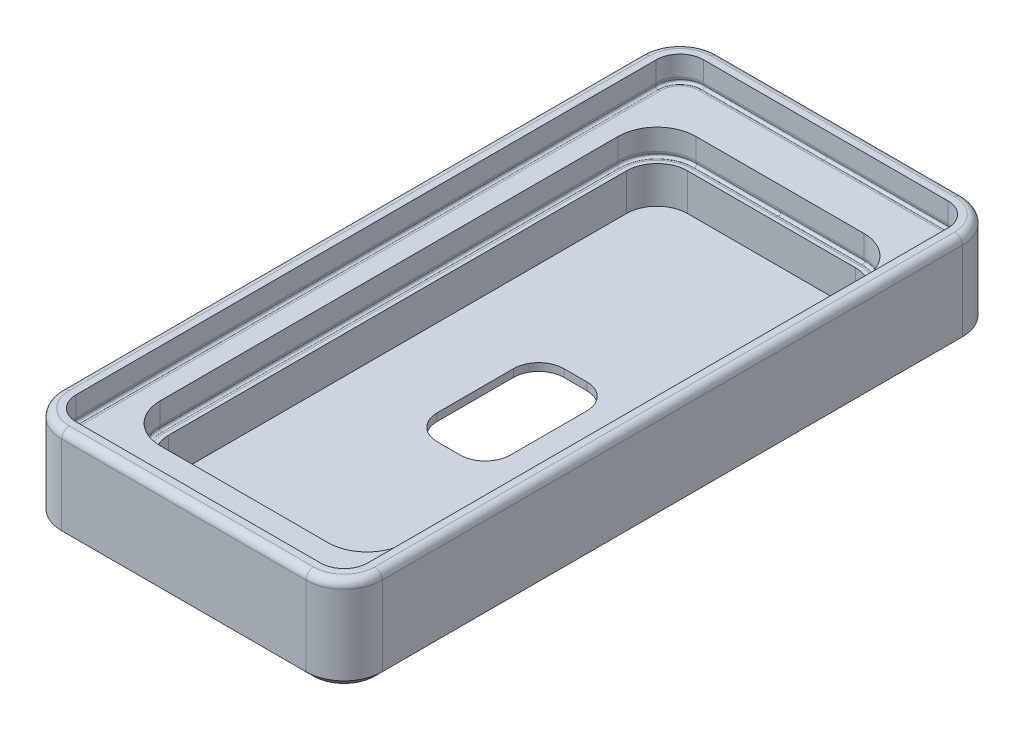
SolidWorks part; units mm, degrees
material "EN8"
ref_plane "Front Plane" through (0, 0, 0) normal (0, 0, 1) x (1, 0, 0)
ref_plane "Top Plane" through (0, 0, 0) normal (0, 1, 0) x (1, 0, 0)
ref_plane "Right Plane" through (0, 0, 0) normal (1, 0, 0) x (0, 0, -1)
sketch "Sketch1" plane through (0, 0, 0) normal (0, 1, 0) x (1, 0, 0)
  line L1 (-16, -43) -> (16, -43)
  line L2 (-21, -38) -> (-21, 38)
  line L3 (-16, 43) -> (16, 43)
  line L4 (21, -38) -> (21, 38)
  line L5 (-21, -43) -> (21, 43) construction
  line L6 (-21, 43) -> (21, -43) construction
  line L7 (16, -35) -> (-16, -35) construction
  line L8 (16, -35) -> (16, 35) construction
  line L9 (16, 35) -> (-16, 35) construction
  line L10 (-16, -35) -> (-16, 35) construction
  line L11 (16, -35) -> (-16, 35) construction
  line L12 (16, 35) -> (-16, -35) construction
  arc A0 (-16, -43) -> (-21, -38) centre (-16, -38) cw
  arc A1 (16, -43) -> (21, -38) centre (16, -38) ccw
  arc A2 (16, 43) -> (21, 38) centre (16, 38) cw
  arc A3 (-21, 38) -> (-16, 43) centre (-16, 38) cw
  point P0 (0, 0)
  point P18 (0, 0)
  dimension "D1" = 5
  dimension "D2" = 8
  dimension "D3" = 32
  dimension "D4" = 70
  dimension "D5" = 5
extrude "Boss-Extrude1" add sketch "Sketch1" along normal blind 9.2
ref_plane "Plane1" through (0, 1, 0) normal (0, 1, 0) x (1, 0, 0)
ref_plane "Plane2" through (0, 5.85, 0) normal (0, 1, 0) x (1, 0, 0)
sketch "Sketch4" plane through (0, 5.85, 0) normal (0, -1, 0) x (-1, 0, 0)
  line L0 (-16, -30) -> (-16, 30)
  line L1 (-11, -35) -> (11, -35) construction
  line L2 (-16, -30) -> (-16, 30) construction
  line L3 (-11, 35) -> (11, 35) construction
  line L4 (16, -30) -> (16, 30) construction
  line L5 (-16, -35) -> (16, 35) construction
  line L6 (-16, 35) -> (16, -35) construction
  line L7 (-11, 35) -> (11, 35)
  line L8 (16, -30) -> (16, 30)
  line L9 (-11, -35) -> (11, -35)
  arc A0 (-11, -35) -> (-16, -30) centre (-11, -30) cw construction
  arc A1 (11, -35) -> (16, -30) centre (11, -30) ccw construction
  arc A2 (11, 35) -> (16, 30) centre (11, 30) cw construction
  arc A3 (-16, 30) -> (-11, 35) centre (-11, 30) cw construction
  arc A4 (-16, 30) -> (-11, 35) centre (-11, 30) cw
  arc A5 (11, 35) -> (16, 30) centre (11, 30) cw
  arc A6 (11, -35) -> (16, -30) centre (11, -30) ccw
  arc A7 (-11, -35) -> (-16, -30) centre (-11, -30) cw
  point P0 (0, 0)
  dimension "D3" = 5
  dimension "D1" = 32
  dimension "D2" = 70
  dimension "D4" = 0
extrude "Cut-Extrude3" cut sketch "Sketch4" against normal through all
sketch "Sketch6" plane through (0, 1, 0) normal (0, 1, 0) x (1, 0, 0)
  line L8 (-11, -34) -> (11, -34)
  line L10 (-15, 30) -> (-15, -30)
  line L16 (11, 34) -> (-11, 34)
  line L18 (15, -30) -> (15, 30)
  line L20 (-11, -34) -> (11, -34)
  line L21 (-15, 30) -> (-15, -30)
  line L22 (11, 34) -> (-11, 34)
  line L23 (15, -30) -> (15, 30)
  arc A12 (11, -34) -> (15, -30) centre (11, -30) ccw
  arc A13 (-15, -30) -> (-11, -34) centre (-11, -30) ccw
  arc A14 (-11, 34) -> (-15, 30) centre (-11, 30) ccw
  arc A15 (15, 30) -> (11, 34) centre (11, 30) ccw
  arc A16 (11, -34) -> (15, -30) centre (11, -30) ccw
  arc A17 (-15, -30) -> (-11, -34) centre (-11, -30) ccw
  arc A18 (-11, 34) -> (-15, 30) centre (-11, 30) ccw
  arc A19 (15, 30) -> (11, 34) centre (11, 30) ccw
  dimension "D1" = 1
extrude "Cut-Extrude4" cut sketch "Sketch6" along normal through all
sketch "Sketch7" plane through (0, 1, 0) normal (0, 1, 0) x (1, 0, 0)
  line L0 (0, 17.5) -> (0, -17.5) construction
  line L1 (-1.5, -10) -> (1.5, -10)
  line L2 (-6.5, -5) -> (-6.5, 5)
  line L3 (-1.5, 10) -> (1.5, 10)
  line L4 (6.5, -5) -> (6.5, 5)
  line L5 (-6.5, -10) -> (6.5, 10) construction
  line L6 (-6.5, 10) -> (6.5, -10) construction
  line L7 (6, 22.5) -> (-6, 22.5)
  line L8 (11, 17.5) -> (11, -17.5)
  line L9 (6, -22.5) -> (-6, -22.5)
  line L10 (-11, 17.5) -> (-11, -17.5)
  line L11 (11, 22.5) -> (-11, -22.5) construction
  line L12 (11, -22.5) -> (-11, 22.5) construction
  arc A0 (-1.5, -10) -> (-6.5, -5) centre (-1.5, -5) cw
  arc A1 (1.5, -10) -> (6.5, -5) centre (1.5, -5) ccw
  arc A2 (1.5, 10) -> (6.5, 5) centre (1.5, 5) cw
  arc A3 (-6.5, 5) -> (-1.5, 10) centre (-1.5, 5) cw
  arc A4 (-6, -22.5) -> (-11, -17.5) centre (-6, -17.5) cw
  arc A5 (11, -17.5) -> (6, -22.5) centre (6, -17.5) cw
  arc A6 (6, 22.5) -> (11, 17.5) centre (6, 17.5) cw
  arc A7 (-6, 22.5) -> (-11, 17.5) centre (-6, 17.5) ccw
  circle A8 centre (0, 17.5) radius 2.5
  circle A9 centre (0, -17.5) radius 2.5
  point P0 (0, 0)
  point P18 (0, 0)
  dimension "D3" = 5
  dimension "D6" = 5
  dimension "D8" = 5
  dimension "D1" = 13
  dimension "D2" = 20
  dimension "D4" = 22
  dimension "D5" = 45
  dimension "D7" = 5
sketch "Sketch8" plane through (0, 1, 0) normal (0, 1, 0) x (1, 0, 0)
  line L4 (1.5, 8.3) -> (-1.5, 8.3)
  line L5 (-4.8, 5) -> (-4.8, -5)
  line L6 (-1.5, -8.3) -> (1.5, -8.3)
  line L7 (4.8, -5) -> (4.8, 5)
  line L8 (-1.5, -9.8) -> (1.5, -9.8)
  line L9 (6.3, -5) -> (6.3, 5)
  line L10 (-6.3, 5) -> (-6.3, -5)
  line L11 (1.5, 9.8) -> (-1.5, 9.8)
  line L12 (-1.5, -9.8) -> (1.5, -9.8)
  line L13 (6.3, -5) -> (6.3, 5)
  line L14 (-6.3, 5) -> (-6.3, -5)
  line L15 (1.5, 9.8) -> (-1.5, 9.8)
  line L20 (-6, -24.2) -> (6, -24.2)
  line L21 (12.7, -17.5) -> (12.7, 17.5)
  line L22 (6, 24.2) -> (-6, 24.2)
  line L23 (-12.7, 17.5) -> (-12.7, -17.5)
  line L24 (-6, -22.7) -> (6, -22.7)
  line L25 (11.2, -17.5) -> (11.2, 17.5)
  line L26 (-11.2, 17.5) -> (-11.2, -17.5)
  line L27 (6, 22.7) -> (-6, 22.7)
  line L28 (-6, -22.7) -> (6, -22.7)
  line L29 (11.2, -17.5) -> (11.2, 17.5)
  line L30 (-11.2, 17.5) -> (-11.2, -17.5)
  line L31 (6, 22.7) -> (-6, 22.7)
  arc A4 (4.8, 5) -> (1.5, 8.3) centre (1.5, 5) ccw
  arc A5 (-1.5, 8.3) -> (-4.8, 5) centre (-1.5, 5) ccw
  arc A6 (-4.8, -5) -> (-1.5, -8.3) centre (-1.5, -5) ccw
  arc A7 (1.5, -8.3) -> (4.8, -5) centre (1.5, -5) ccw
  arc A8 (-6.3, -5) -> (-1.5, -9.8) centre (-1.5, -5) ccw
  arc A9 (1.5, -9.8) -> (6.3, -5) centre (1.5, -5) ccw
  arc A10 (6.3, 5) -> (1.5, 9.8) centre (1.5, 5) ccw
  arc A11 (-1.5, 9.8) -> (-6.3, 5) centre (-1.5, 5) ccw
  arc A12 (-6.3, -5) -> (-1.5, -9.8) centre (-1.5, -5) ccw
  arc A13 (1.5, -9.8) -> (6.3, -5) centre (1.5, -5) ccw
  arc A14 (6.3, 5) -> (1.5, 9.8) centre (1.5, 5) ccw
  arc A15 (-1.5, 9.8) -> (-6.3, 5) centre (-1.5, 5) ccw
  arc A20 (-12.7, -17.5) -> (-6, -24.2) centre (-6, -17.5) ccw
  arc A21 (6, -24.2) -> (12.7, -17.5) centre (6, -17.5) ccw
  arc A22 (12.7, 17.5) -> (6, 24.2) centre (6, 17.5) ccw
  arc A23 (-6, 24.2) -> (-12.7, 17.5) centre (-6, 17.5) ccw
  arc A24 (-11.2, -17.5) -> (-6, -22.7) centre (-6, -17.5) ccw
  arc A25 (6, -22.7) -> (11.2, -17.5) centre (6, -17.5) ccw
  arc A26 (11.2, 17.5) -> (6, 22.7) centre (6, 17.5) ccw
  arc A27 (-6, 22.7) -> (-11.2, 17.5) centre (-6, 17.5) ccw
  arc A28 (-11.2, -17.5) -> (-6, -22.7) centre (-6, -17.5) ccw
  arc A29 (6, -22.7) -> (11.2, -17.5) centre (6, -17.5) ccw
  arc A30 (11.2, 17.5) -> (6, 22.7) centre (6, 17.5) ccw
  arc A31 (-6, 22.7) -> (-11.2, 17.5) centre (-6, 17.5) ccw
  circle A38 centre (0, 17.5) radius 3
  circle A39 centre (0, 17.5) radius 3
  circle A41 centre (0, -17.5) radius 3
  circle A42 centre (0, -17.5) radius 3
  dimension "D1" = 0.2
  dimension "D2" = 1.5
  dimension "D3" = 0.2
  dimension "D4" = 1.5
  dimension "D5" = 0.5
  dimension "D6" = 0.5
extrude "Cut-Extrude5" cut sketch "Sketch8" against normal blind 2 contours L6 A7 L7 A4 L4 A5 L5 A6 region at (0, 1, 0)
sketch "Sketch9" plane through (0, 9.2, 0) normal (0, 1, 0) x (1, 0, 0)
  line L8 (-16, -41) -> (16, -41)
  line L9 (19, -38) -> (19, 38)
  line L10 (-19, 38) -> (-19, -38)
  line L11 (16, 41) -> (-16, 41)
  line L12 (-16, -41) -> (16, -41)
  line L13 (19, -38) -> (19, 38)
  line L14 (-19, 38) -> (-19, -38)
  line L15 (16, 41) -> (-16, 41)
  line L16 (-16, -43) -> (16, -43)
  line L17 (21, -38) -> (21, 38)
  line L18 (16, 43) -> (-16, 43)
  line L19 (-21, 38) -> (-21, -38)
  line L20 (-16, -43) -> (16, -43)
  line L21 (21, -38) -> (21, 38)
  line L22 (16, 43) -> (-16, 43)
  line L23 (-21, 38) -> (-21, -38)
  arc A8 (-19, -38) -> (-16, -41) centre (-16, -38) ccw
  arc A9 (16, -41) -> (19, -38) centre (16, -38) ccw
  arc A10 (19, 38) -> (16, 41) centre (16, 38) ccw
  arc A11 (-16, 41) -> (-19, 38) centre (-16, 38) ccw
  arc A12 (-19, -38) -> (-16, -41) centre (-16, -38) ccw
  arc A13 (16, -41) -> (19, -38) centre (16, -38) ccw
  arc A14 (19, 38) -> (16, 41) centre (16, 38) ccw
  arc A15 (-16, 41) -> (-19, 38) centre (-16, 38) ccw
  arc A16 (-21, -38) -> (-16, -43) centre (-16, -38) ccw
  arc A17 (16, -43) -> (21, -38) centre (16, -38) ccw
  arc A18 (21, 38) -> (16, 43) centre (16, 38) ccw
  arc A19 (-16, 43) -> (-21, 38) centre (-16, 38) ccw
  arc A20 (-21, -38) -> (-16, -43) centre (-16, -38) ccw
  arc A21 (16, -43) -> (21, -38) centre (16, -38) ccw
  arc A22 (21, 38) -> (16, 43) centre (16, 38) ccw
  arc A23 (-16, 43) -> (-21, 38) centre (-16, 38) ccw
  dimension "D1" = 2
  dimension "D2" = 0
extrude "Boss-Extrude3" add sketch "Sketch9" along normal blind 3.2
fillet "Fillet3" radius 1 8 edges at (21, 12.4, 0) (19.5355, 12.4, 41.5355) (0, 12.4, 43) (-19.5355, 12.4, 41.5355) (-21, 12.4, 0) (-19.5355, 12.4, -41.5355) (0, 12.4, -43) (19.5355, 12.4, -41.5355)
sketch "Sketch10" plane through (0, 0, 0) normal (1, 0, 0) x (0, 0, -1)
  line L0 (-30, 5.85) -> (30, 5.85) construction
  line L1 (-30, 5.85) -> (30, 5.85) construction
  line L2 (-30, 9.2) -> (30, 9.2) construction
  line L3 (-30, 9.2) -> (30, 9.2) construction
  line L4 (-25, 9.2) -> (-25, 5.85) construction
  circle A0 centre (-25, 7.525) radius 1.5
  dimension "D1" = 3
  dimension "D2" = 25
sketch "Sketch11" plane through (0, 5.85, 0) normal (0, 1, 0) x (1, 0, 0)
  line L0 (16.1, -30) -> (16.1, 30)
  line L1 (11, 35.1) -> (-11, 35.1)
  line L2 (-16.1, 30) -> (-16.1, -30)
  line L3 (-11, -35.1) -> (11, -35.1)
  line L4 (16, -30) -> (16, 30)
  line L5 (11, 35) -> (-11, 35)
  line L6 (-16, 30) -> (-16, -30)
  line L7 (-11, -35) -> (11, -35)
  line L8 (16, -30) -> (16, 30)
  line L9 (11, 35) -> (-11, 35)
  line L10 (-16, 30) -> (-16, -30)
  line L11 (-11, -35) -> (11, -35)
  arc A0 (16.1, 30) -> (11, 35.1) centre (11, 30) ccw
  arc A1 (-11, 35.1) -> (-16.1, 30) centre (-11, 30) ccw
  arc A2 (-16.1, -30) -> (-11, -35.1) centre (-11, -30) ccw
  arc A3 (11, -35.1) -> (16.1, -30) centre (11, -30) ccw
  arc A4 (11, -35) -> (16, -30) centre (11, -30) ccw
  arc A5 (16, 30) -> (11, 35) centre (11, 30) ccw
  arc A6 (-11, 35) -> (-16, 30) centre (-11, 30) ccw
  arc A7 (-16, -30) -> (-11, -35) centre (-11, -30) ccw
  arc A8 (11, -35) -> (16, -30) centre (11, -30) ccw
  arc A9 (16, 30) -> (11, 35) centre (11, 30) ccw
  arc A10 (-11, 35) -> (-16, 30) centre (-11, 30) ccw
  arc A11 (-16, -30) -> (-11, -35) centre (-11, -30) ccw
  dimension "D1" = 0
  dimension "D2" = 0.1
extrude "Cut-Extrude7" cut sketch "Sketch11" along normal through all
sketch "Sketch12" plane through (0, 9.2, 0) normal (0, 1, 0) x (1, 0, 0)
  line L0 (-19.1, 38) -> (-19.1, -38)
  line L1 (-16, -41.1) -> (16, -41.1)
  line L2 (19.1, -38) -> (19.1, 38)
  line L3 (16, 41.1) -> (-16, 41.1)
  line L4 (-19, 38) -> (-19, -38)
  line L5 (-16, -41) -> (16, -41)
  line L6 (19, -38) -> (19, 38)
  line L7 (16, 41) -> (-16, 41)
  line L8 (-19, 38) -> (-19, -38)
  line L9 (-16, -41) -> (16, -41)
  line L10 (19, -38) -> (19, 38)
  line L11 (16, 41) -> (-16, 41)
  arc A0 (-19.1, -38) -> (-16, -41.1) centre (-16, -38) ccw
  arc A1 (16, -41.1) -> (19.1, -38) centre (16, -38) ccw
  arc A2 (19.1, 38) -> (16, 41.1) centre (16, 38) ccw
  arc A3 (-16, 41.1) -> (-19.1, 38) centre (-16, 38) ccw
  arc A4 (-19, -38) -> (-16, -41) centre (-16, -38) ccw
  arc A5 (16, -41) -> (19, -38) centre (16, -38) ccw
  arc A6 (19, 38) -> (16, 41) centre (16, 38) ccw
  arc A7 (-16, 41) -> (-19, 38) centre (-16, 38) ccw
  arc A8 (-19, -38) -> (-16, -41) centre (-16, -38) ccw
  arc A9 (16, -41) -> (19, -38) centre (16, -38) ccw
  arc A10 (19, 38) -> (16, 41) centre (16, 38) ccw
  arc A11 (-16, 41) -> (-19, 38) centre (-16, 38) ccw
  dimension "D1" = 0
  dimension "D2" = 0.1
extrude "Cut-Extrude8" cut sketch "Sketch12" along normal through all
sketch "Sketch13" plane through (0, 0, 0) normal (1, 0, 0) x (0, 0, -1)
  line L0 (36.1672, 9.2) -> (41.1, 9.2) construction
  line L2 (41.1, 9.2) -> (41.1, 9.966) construction
  line L3 (41.1, 12.4) -> (41.1, 9.2) construction
  line L4 (-30, 9.2) -> (-35.1, 9.2) construction
  line L5 (41.1, 9.2) -> (40.9586, 9.3414) construction
  circle A1 centre (40.9586, 9.3414) radius 0.25
  dimension "D1" = 45
  dimension "D2" = 0.5
  dimension "D3" = 0.2
sketch "Sketch14" plane through (0, 9.2, 0) normal (0, 1, 0) x (1, 0, 0)
  line L4 (-19.1, 38) -> (-19.1, -38)
  line L5 (-16, -41.1) -> (16, -41.1)
  line L6 (19.1, -38) -> (19.1, 38)
  line L7 (16, 41.1) -> (-16, 41.1)
  line L8 (-19.1, 38) -> (-19.1, -38)
  line L9 (-16, -41.1) -> (16, -41.1)
  line L10 (19.1, -38) -> (19.1, 38)
  line L11 (16, 41.1) -> (-16, 41.1)
  arc A4 (-16, 41.1) -> (-19.1, 38) centre (-16, 38) ccw
  arc A5 (-19.1, -38) -> (-16, -41.1) centre (-16, -38) ccw
  arc A6 (16, -41.1) -> (19.1, -38) centre (16, -38) ccw
  arc A7 (19.1, 38) -> (16, 41.1) centre (16, 38) ccw
  arc A8 (-16, 41.1) -> (-19.1, 38) centre (-16, 38) ccw
  arc A9 (-19.1, -38) -> (-16, -41.1) centre (-16, -38) ccw
  arc A10 (16, -41.1) -> (19.1, -38) centre (16, -38) ccw
  arc A11 (19.1, 38) -> (16, 41.1) centre (16, 38) ccw
  dimension "D1" = 0
sweep "Cut-Sweep1" cut profiles "Sketch13" path "Sketch14"
sketch "Sketch15" plane through (0, 0, 0) normal (1, 0, 0) x (0, 0, -1)
  line L0 (32.6053, 5.85) -> (35.1, 5.85) construction
  line L1 (35.1, 5.85) -> (35.1, 6.8847) construction
  line L3 (35.1, 9.2) -> (35.1, 5.85) construction
  line L4 (-30, 5.85) -> (-34, 5.85) construction
  line L5 (35.1, 5.85) -> (34.9586, 5.9914) construction
  circle A0 centre (34.9586, 5.9914) radius 0.25
  dimension "D2" = 0.5
  dimension "D1" = 45
  dimension "D3" = 0.2
sketch "Sketch16" plane through (0, 5.85, 0) normal (0, 1, 0) x (1, 0, 0)
  line L4 (16.1, -30) -> (16.1, 30)
  line L5 (11, 35.1) -> (-11, 35.1)
  line L6 (-16.1, 30) -> (-16.1, -30)
  line L7 (-11, -35.1) -> (11, -35.1)
  line L8 (16.1, -30) -> (16.1, 30)
  line L9 (11, 35.1) -> (-11, 35.1)
  line L10 (-16.1, 30) -> (-16.1, -30)
  line L11 (-11, -35.1) -> (11, -35.1)
  arc A4 (11, -35.1) -> (16.1, -30) centre (11, -30) ccw
  arc A5 (16.1, 30) -> (11, 35.1) centre (11, 30) ccw
  arc A6 (-11, 35.1) -> (-16.1, 30) centre (-11, 30) ccw
  arc A7 (-16.1, -30) -> (-11, -35.1) centre (-11, -30) ccw
  arc A8 (11, -35.1) -> (16.1, -30) centre (11, -30) ccw
  arc A9 (16.1, 30) -> (11, 35.1) centre (11, 30) ccw
  arc A10 (-11, 35.1) -> (-16.1, 30) centre (-11, 30) ccw
  arc A11 (-16.1, -30) -> (-11, -35.1) centre (-11, -30) ccw
  dimension "D1" = 0
sweep "Cut-Sweep2" cut profiles "Sketch15" path "Sketch16"
fillet "Fillet4" radius 0.75 36 edges at (-18.192, 9.5476, -40.192) (-19.1, 9.5476, 0) (-18.192, 9.5476, 40.192) (0, 9.5476, 41.1) (18.192, 9.5476, 40.192) (19.1, 9.5476, 0) (18.192, 9.5476, -40.192) (8, 9.5476, -41.1) (-17.9463, 9.2, -39.9463) (-18.7524, 9.2, 0) (-17.9463, 9.2, 39.9463) (0, 9.2, 40.7524) (17.9463, 9.2, 39.9463) (18.7524, 9.2, 0) (17.9463, 9.2, -39.9463) (8, 9.2, -40.7524) (-8, 9.5476, -41.1) (-8, 9.2, -40.7524) (-14.3605, 5.85, -33.3605) (-15.7524, 5.85, 0) (-14.3605, 5.85, 33.3605) (0, 5.85, 34.7524) (14.3605, 5.85, 33.3605) (15.7524, 5.85, 0) (14.3605, 5.85, -33.3605) (5.5, 5.85, -34.7524) (5.5, 6.1976, -35.1) (14.6062, 6.1976, -33.6062) (16.1, 6.1976, 0) (14.6062, 6.1976, 33.6062) (0, 6.1976, 35.1) (-14.6062, 6.1976, 33.6062) (-16.1, 6.1976, 0) (-14.6062, 6.1976, -33.6062) (-5.5, 5.85, -34.7524) (-5.5, 6.1976, -35.1)
sketch "Sketch17" plane through (0, 0, 0) normal (0, -1, 0) x (1, 0, 0)
  line L0 (16, 43) -> (-16, 43) construction
  line L1 (16, -38) -> (-16, -38) construction
  line L2 (16, -38) -> (16, 38) construction
  line L3 (16, 38) -> (-16, 38) construction
  line L4 (-16, -38) -> (-16, 38) construction
  line L5 (16, -38) -> (-16, 38) construction
  line L6 (16, 38) -> (-16, -38) construction
  line L7 (21, -38) -> (21, 38) construction
  circle A0 centre (-16, 38) radius 3.085
  circle A1 centre (16, 38) radius 3.085
  circle A2 centre (16, -38) radius 3.085
  circle A3 centre (-16, -38) radius 3.085
  point P0 (0, 0)
  dimension "D1" = 6.17
  dimension "D2" = 5
  dimension "D3" = 5
extrude "Cut-Extrude9" cut sketch "Sketch17" against normal blind 8.2
chamfer "Chamfer1" distance 1 angle 45 8 edges at (21, 0, 0) (19.5355, 0, -41.5355) (19.5355, 0, 41.5355) (0, 0, -43) (0, 0, 43) (-19.5355, 0, -41.5355) (-19.5355, 0, 41.5355) (-21, 0, 0)
